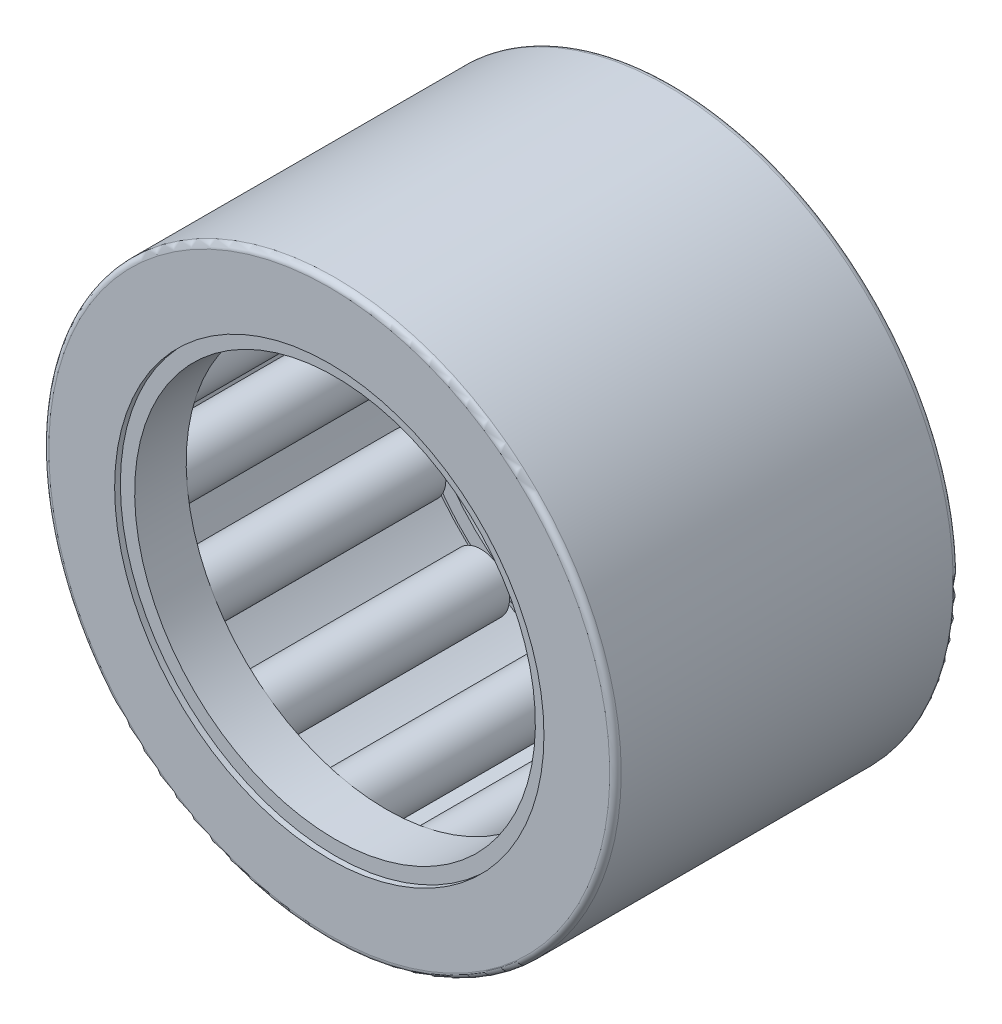
SolidWorks part; units mm, degrees
ref_plane "Front Plane" through (0, 0, 0) normal (0, 0, 1) x (1, 0, 0)
ref_plane "Top Plane" through (0, 0, 0) normal (0, 1, 0) x (1, 0, 0)
ref_plane "Right Plane" through (0, 0, 0) normal (1, 0, 0) x (0, 0, -1)
sketch "Sketch1" plane through (0, 0, 0) normal (1, 0, 0) x (0, 0, -1)
  line L0 (-6, 0) -> (6, 0) construction
  line L1 (0, 0) -> (0, 10) construction
  line L2 (-6, 0) -> (-6, 10) construction
  line L3 (-6, 10) -> (6, 10)
  line L4 (6, 10) -> (6, 0) construction
  line L5 (6, 0) -> (5, 0) construction
  line L6 (5, 0) -> (5, 9) construction
  line L7 (5, 9) -> (-5, 9)
  line L8 (-5, 9) -> (-5, 0) construction
  line L9 (-5, 0) -> (-6, 0) construction
  line L10 (-6, 10) -> (-6, 7.5)
  line L11 (-6, 7.5) -> (-5, 7.5)
  line L12 (-5, 7.5) -> (-5, 9)
  line L13 (5, 10) -> (5, 9) construction
  line L14 (5, 9) -> (5, 7.5)
  line L15 (5, 7.5) -> (6, 7.5)
  line L16 (6, 7.5) -> (6, 10)
  line L17 (5, 9) -> (5, 8) construction
  line L18 (5, 8) -> (5, 7) construction
  line L19 (5, -9) -> (5, -8) construction
  line L20 (5, -10) -> (5, -9) construction
  line L21 (6, -7.5) -> (6, -10) construction
  line L22 (5, -7.5) -> (6, -7.5) construction
  line L23 (5, -9) -> (5, -7.5) construction
  line L24 (-5, -7.5) -> (-5, -9) construction
  line L25 (-6, -7.5) -> (-5, -7.5) construction
  line L26 (-6, -10) -> (-6, -7.5) construction
  line L27 (5, -9) -> (-5, -9) construction
  line L28 (-6, -10) -> (6, -10) construction
  point P4 (0, 7)
  dimension "C | Width" = 12
  dimension "Fw | ID" = 14
  dimension "D | OD" = 20
sketch "Sketch7" plane through (0, 0, 0) normal (1, 0, 0) x (0, 0, -1)
  line L0 (-6, 10) -> (-6, 7.5) construction
  line L1 (-6, 7.5) -> (-5, 7.5) construction
  line L2 (-5, 7.5) -> (-5, 9) construction
  line L3 (5, 9) -> (-5, 9) construction
  line L4 (5, 9) -> (5, 7.5) construction
  line L5 (5, 7.5) -> (6, 7.5) construction
  line L6 (6, 7.5) -> (6, 10) construction
  line L8 (-6, 10) -> (6, 10) construction
  line L9 (-6, 10) -> (-6, 7.5)
  line L10 (-6, 7.5) -> (-5, 7.5)
  line L13 (-5, 7.5) -> (-5, 9)
  line L16 (5, 9) -> (-5, 9)
  line L17 (5, 9) -> (5, 7.5)
  line L18 (5, 7.5) -> (6, 7.5)
  line L19 (6, 7.5) -> (6, 10)
  line L20 (-6, 10) -> (6, 10)
revolve "Revolve1" add sketch "Sketch7" angle 360 about L0
sketch "Sketch2" plane through (0, 0, 0) normal (1, 0, 0) x (0, 0, -1)
  line L0 (-6, 7.5) -> (-5, 7.5) construction
  line L1 (-4, 8) -> (4, 8) construction
  line L2 (-4, 8) -> (-4, 9) construction
  line L3 (-4, 9) -> (4, 9)
  line L4 (4, 8) -> (4, 9) construction
  line L5 (5, 7.5) -> (6, 7.5) construction
  line L6 (-5, 8) -> (-4, 8) construction
  line L7 (4, 8) -> (5, 8) construction
  line L8 (6, 10) -> (6, 0) construction
  line L9 (-4, 8.25) -> (-4, 7.75) construction
  line L10 (-5, 8) -> (-5, 7.5) construction
  line L11 (-4, 9) -> (-4, 8.25)
  line L12 (4, 9) -> (4, 8.25)
  line L13 (4, 8.25) -> (-4, 8.25)
  line L14 (0, 9) -> (0, 7) construction
  line L16 (-4, 7.75) -> (-5, 7.75) construction
  line L17 (0, 0) -> (6, 0) construction
  line L18 (-4, -7.75) -> (-5, -7.75) construction
  line L19 (0, -9) -> (0, -7) construction
  line L20 (-5, -8) -> (-5, -7.5) construction
  line L21 (-4, -8.25) -> (-4, -7.75) construction
  line L22 (4, -8) -> (5, -8) construction
  line L23 (-5, -8) -> (-4, -8) construction
  line L24 (4, -8) -> (4, -9) construction
  line L25 (-4, -8) -> (-4, -9) construction
  line L26 (-4, -8) -> (4, -8) construction
  line L27 (4, -8.25) -> (-4, -8.25) construction
  line L28 (4, -9) -> (4, -8.25) construction
  line L29 (-4, -9) -> (-4, -8.25) construction
  line L30 (-4, -9) -> (4, -9) construction
  line L33 (5, 9) -> (-5, 9) construction
  line L34 (5, 9) -> (5, 7.5) construction
  line L35 (-5, 7.5) -> (-5, 9) construction
  line L36 (0, 0) -> (0, 10) construction
  point P16 (0, 8)
revolve "Revolve2" add sketch "Sketch2" angle 360 about L1
sketch "Sketch3" plane through (0, 0, 0) normal (1, 0, 0) x (0, 0, -1)
  line L1 (-5, 8) -> (5, 8)
  line L2 (-5, 8) -> (-5, 8.25)
  line L3 (-5, 8.25) -> (5, 8.25)
  line L4 (5, 8) -> (5, 8.25)
  line L5 (0, 0) -> (6, 0) construction
  line L7 (5, -8) -> (5, -8.25) construction
  line L8 (-5, -8.25) -> (5, -8.25) construction
  line L9 (-5, -8) -> (-5, -8.25) construction
  line L10 (-5, -8) -> (5, -8) construction
  line L11 (5, 9) -> (5, 7.5) construction
  line L12 (6, 10) -> (6, 0) construction
revolve "Revolve3" add sketch "Sketch3" angle 360 about L1
ref_axis "Axis1" through (0, 7.5, 6) along (0, 1, 0)
pattern_circular "CirPattern1" count 15 every 24 about axis through (0, 0, 6) along (0, 0, -1) of bodies 166 167
fillet "Fillet1" radius 0.2 2 edges at (0, -10, -6) (0, -10, 6)
sketch "Sketch4" plane through (0, 0, 0) normal (1, 0, 0) x (0, 0, -1)
  line L0 (4, 9) -> (4, 8.25) construction
  line L1 (5.8, 7) -> (4, 7)
  line L2 (5.8, 7) -> (5.8, 7.5)
  line L3 (5.8, 7.5) -> (4, 7.5)
  line L4 (4, 7) -> (4, 7.5)
  line L7 (5, 7.5) -> (6, 7.5) construction
  line L8 (5.8, -10) -> (5.8, 10) construction
revolve "Revolve4" add sketch "Sketch4" angle 360 about L0
sketch "Sketch5" plane through (0, 0, 0) normal (1, 0, 0) x (0, 0, -1)
  line L0 (-5.8, 10) -> (-5.8, -10) construction
  line L1 (-4, 7) -> (-5.8, 7)
  line L2 (-4, 7) -> (-4, 7.5)
  line L3 (-4, 7.5) -> (-5.8, 7.5)
  line L4 (-5.8, 7) -> (-5.8, 7.5)
  line L5 (-4, 9) -> (-4, 8.25) construction
  line L6 (-6, 7.5) -> (-5, 7.5) construction
revolve "Revolve5" add sketch "Sketch5" angle 360 about L0
sketch "Front View" plane through (0, 0, 0) normal (0, 0, 1) x (1, 0, 0)
  circle A0 centre (0, 0) radius 7 construction
  circle A1 centre (0, 0) radius 10 construction
  dimension "ID" = 14
  dimension "OD" = 20
sketch "Right View" plane through (0, 0, 0) normal (1, 0, 0) x (0, 0, -1)
  line L0 (-6, 10) -> (6, 10) construction
  line L1 (-6, 10) -> (6, 10) construction
  line L2 (0, 0) -> (0, 10) construction
  point P4 (0, 10)
  dimension "Width" = 12
equation "\"Rollers@CirPattern1\"  = \"OD@Sketch1\"*.75"
equation "\"D1@Fillet1\" = \"D | OD@Sketch1\" * .01"
equation "\"Angle@CirPattern1\"=360 / \"Rollers@CirPattern1\""
equation "\"ID@Front View\" = \"Fw | ID@Sketch1\""
equation "\"OD@Front View\" = \"D | OD@Sketch1\""
equation "\"Width@Right View\" = \"C | Width@Sketch1\""
